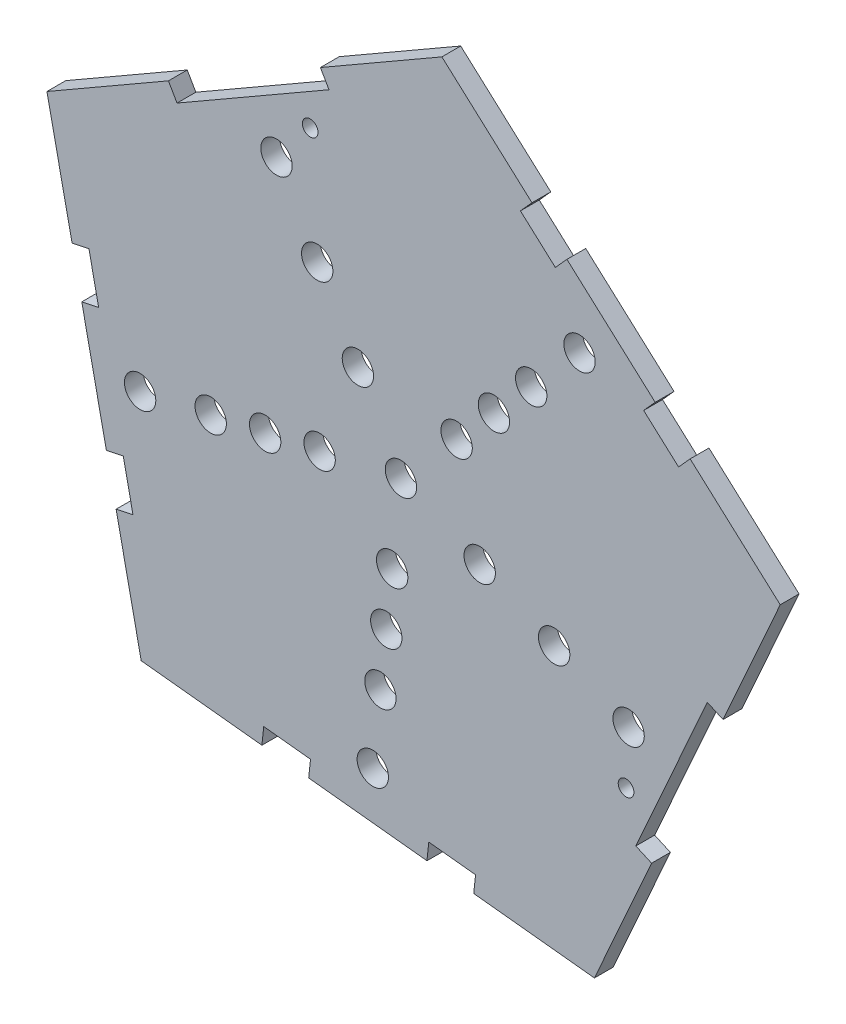
SolidWorks part; units mm, degrees
ref_plane "Front Plane" through (0, 0, 0) normal (0, 0, 1) x (1, 0, 0)
ref_plane "Top Plane" through (0, 0, 0) normal (0, 1, 0) x (1, 0, 0)
ref_plane "Right Plane" through (0, 0, 0) normal (1, 0, 0) x (0, 0, -1)
sketch "Sketch1" plane through (0, 0, 0) normal (0, 0, 1) x (1, 0, 0)
  line L1 (-82.808, -91.7686) -> (61.688, -107.1132)
  line L2 (61.688, -107.1132) -> (120.9333, 25.569)
  line L3 (120.9333, 25.569) -> (13.0529, 122.9157)
  line L4 (13.0529, 122.9157) -> (-112.8662, 50.3971)
  line L5 (-112.8662, 50.3971) -> (-82.808, -91.7686)
  circle A0 centre (0, 0) radius 100 construction
extrude "Boss-Extrude1" add sketch "Sketch1" along normal blind 6 contours L4 L5 L1 L2 L3
sketch "Sketch2" plane through (0, 0, 6) normal (0, 0, 1) x (1, 0, 0)
  line L0 (3.3497, 3.7121) -> (0, 0) construction
  line L2 (4.5655, -2.0386) -> (0, 0) construction
  line L5 (-2.4953, 4.3328) -> (0, 0) construction
  line L7 (0, 0) -> (-4.8919, -1.0343) construction
  line L8 (0, 0) -> (-0.528, -4.972) construction
  circle A6 centre (0, 0) radius 5
extrude "Cut-Extrude1" cut sketch "Sketch2" against normal blind 6 contours A6
sketch "Sketch8" plane through (0, 0, 6) normal (0, 0, 1) x (1, 0, 0)
  line L4 (-82.808, -91.7686) -> (61.688, -107.1132) construction
  line L5 (16.0987, -27.9532) -> (31.5598, 6.6727)
  line L6 (31.5598, 6.6727) -> (3.4064, 32.0772)
  line L8 (3.4064, 32.0772) -> (-29.4546, 13.1521)
  line L9 (-29.4546, 13.1521) -> (-21.6103, -23.9488)
  line L10 (-21.6103, -23.9488) -> (16.0987, -27.9532)
  line L11 (-21.6103, -23.9488) -> (-29.4145, -97.4386)
  line L12 (16.0987, -27.9532) -> (8.2945, -101.4431)
  line L13 (16.0987, -27.9532) -> (83.5801, -58.085)
  line L14 (61.688, -107.1132) -> (120.9333, 25.569) construction
  line L15 (31.5598, 6.6727) -> (99.0413, -23.4591)
  line L16 (31.5598, 6.6727) -> (81.0698, 61.5401)
  line L17 (120.9333, 25.569) -> (13.0529, 122.9157) construction
  line L18 (3.4064, 32.0772) -> (52.9164, 86.9446)
  line L19 (3.4064, 32.0772) -> (-33.4762, 96.1189)
  line L20 (13.0529, 122.9157) -> (-112.8662, 50.3971) construction
  line L21 (-29.4546, 13.1521) -> (-66.3371, 77.1938)
  line L22 (13.0529, 122.9157) -> (-112.8662, 50.3971) construction
  line L23 (-29.4546, 13.1521) -> (-101.7592, -2.1354)
  line L24 (-112.8662, 50.3971) -> (-82.808, -91.7686) construction
  line L25 (-21.6103, -23.9488) -> (-93.915, -39.2362)
  line L26 (16.0987, -27.9532) -> (12.4292, -36.1712) construction
  line L27 (31.5598, 6.6727) -> (35.2293, 14.8907) construction
  line L28 (12.4292, -36.1712) -> (79.9106, -66.303)
  line L29 (35.2293, 14.8907) -> (102.7107, -15.2411)
  circle A0 centre (0, 0) radius 32.2575 construction
  dimension "D1" = 9
  dimension "D2" = 9
sketch "Sketch11" plane through (0, 0, 6) normal (0, 0, 1) x (1, 0, 0)
  line L0 (-8.976, -84.5247) -> (-6.5472, -61.6533) construction
  line L1 (-21.6103, -23.9488) -> (-29.4145, -97.4386) construction
  line L2 (-6.5472, -61.6533) -> (-4.6728, -44.0026) construction
  line L3 (-4.6728, -44.0026) -> (-2.7984, -26.3518) construction
  line L4 (8.2945, -101.4431) -> (8.8753, -95.9738)
  line L5 (8.2945, -101.4431) -> (23.2106, -103.0271)
  line L6 (8.8753, -95.9738) -> (23.7914, -97.5578)
  line L7 (23.2106, -103.0271) -> (23.7914, -97.5578)
  line L8 (-29.4145, -97.4386) -> (-28.8337, -91.9694)
  line L9 (-28.8337, -91.9694) -> (-43.7498, -90.3854)
  line L10 (-44.3306, -95.8546) -> (-43.7498, -90.3854)
  line L11 (-29.4145, -97.4386) -> (-44.3306, -95.8546)
  line L12 (-82.808, -91.7686) -> (61.688, -107.1132) construction
  circle A0 centre (0, 0) radius 62
  circle A1 centre (-6.5472, -61.6533) radius 5
  circle A2 centre (0, 0) radius 44.25
  circle A3 centre (-4.6728, -44.0026) radius 5
  circle A4 centre (0, 0) radius 26.5
  circle A5 centre (-2.7984, -26.3518) radius 5
  circle A6 centre (-8.976, -84.5247) radius 5
  dimension "D2" = 17.75
  dimension "D3" = 17.75
  dimension "D1" = 23
extrude "Cut-Extrude2" cut sketch "Sketch11" against normal blind 10 contours A2 A3 | A2 A3 | A4 A5 | A4 A5 | A1 | A6 region at (-4.4434, -41.8426, 6) region at (-4.8914, -46.0614, 6) region at (-2.5656, -24.1594, 6) region at (-3.0133, -28.3753, 6)
sketch "Sketch12" plane through (0, 0, 6) normal (0, 0, 1) x (1, 0, 0)
  line L0 (72.592, -32.4138) -> (48.8512, -21.8131) construction
  line L1 (16.0987, -27.9532) -> (83.5801, -58.085) construction
  line L2 (48.8512, -21.8131) -> (25.1104, -11.2123) construction
  line L3 (31.5598, 6.6727) -> (99.0413, -23.4591) construction
  circle A0 centre (0, 0) radius 53.5
  circle A1 centre (48.8512, -21.8131) radius 5
  circle A2 centre (0, 0) radius 27.5
  circle A3 centre (25.1104, -11.2123) radius 5
  circle A5 centre (84.8224, -20.3523) radius 2.5
  circle A6 centre (72.592, -32.4138) radius 5
  dimension "D2" = 26
  dimension "D1" = 26
extrude "Cut-Extrude3" cut sketch "Sketch12" against normal blind 10 contours A2 A3 | A6 | A1 | A3 | A5 region at (26.9714, -12.0433, 6) region at (72.592, -32.4138, 6)
extrude "Cut-Extrude4" cut sketch "Sketch11<3>" against normal blind 10 contours L6 L7 L5 L4 | L11 L10 L9 L8
sketch "Sketch11<3>" plane through (0, 0, 6) normal (0, 0, 1) x (1, 0, 0) same geometry as "Sketch11"
ref_plane "Plane4" through (0, 0, 0) normal (-0.4077, -0.9131, 0) x (-0.9131, 0.4077, 0)
ref_plane "Plane5" through (0, 0, 0) normal (0.7424, -0.6699, 0) x (0, 0, -1)
mirror "Mirror3" about plane through (0, 0, 0) normal (-0.4077, -0.9131, 0) of "Cut-Extrude2"
mirror "Mirror4" about plane through (0, 0, 0) normal (0.7424, -0.6699, 0) of "Cut-Extrude3"
mirror "Mirror5" about plane through (0, 0, 0) normal (0.7424, -0.6699, 0) of "Cut-Extrude2"
mirror "Mirror6" about plane through (0, 0, 0) normal (-0.4077, -0.9131, 0) of "Cut-Extrude4"
mirror "Mirror7" about plane through (0, 0, 0) normal (0.7424, -0.6699, 0) of "Cut-Extrude4"
sketch "Sketch13" plane through (0, 0, 6) normal (0, 0, 1) x (1, 0, 0)
  line L0 (79.9106, -66.303) -> (102.7107, -15.2411)
  line L1 (79.9106, -66.303) -> (74.8885, -64.0605)
  line L2 (102.7107, -15.2411) -> (97.6887, -12.9987)
  line L3 (74.8885, -64.0605) -> (97.6887, -12.9987)
extrude "Cut-Extrude5" cut sketch "Sketch13" against normal blind 10 contours L3 L2 L0 L1
mirror "Mirror8" about plane through (0, 0, 0) normal (0.7424, -0.6699, 0) of "Cut-Extrude5"
sketch "Sketch14" plane through (0, 0, 0) normal (0, 0, -1) x (-1, 0, 0)
  line L0 (-3.0133, -1.3455) -> (3.0133, 1.3455) construction
  circle A0 centre (-84.8224, -20.3523) radius 2.5
  circle A1 centre (-71.7754, -49.5718) radius 2.5
extrude "Boss-Extrude2" add sketch "Sketch14" against normal blind 6 contours A0 region at (84.8224, -20.3523, 0)
extrude "Cut-Extrude6" cut sketch "Sketch14<3>" against normal blind 6 contours A1
sketch "Sketch14<3>" plane through (0, 0, 0) normal (0, 0, -1) x (-1, 0, 0) same geometry as "Sketch14"
